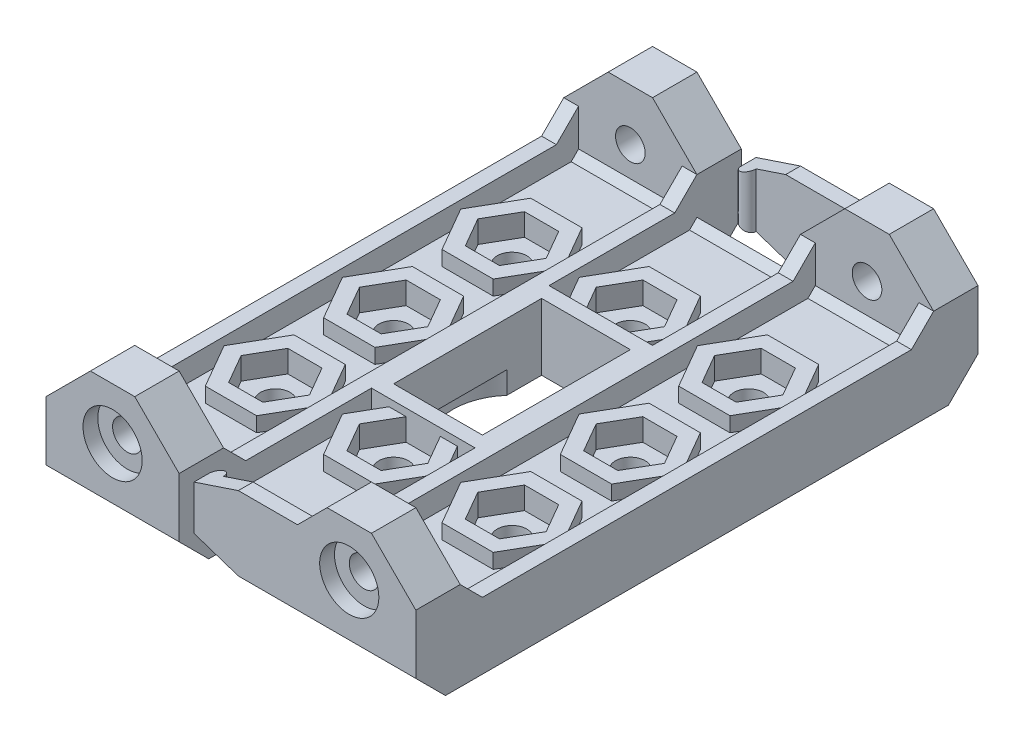
SolidWorks part; units mm, degrees
ref_plane "Front Plane" through (0, 0, 0) normal (0, 0, 1) x (1, 0, 0)
ref_plane "Top Plane" through (0, 0, 0) normal (0, 1, 0) x (1, 0, 0)
ref_plane "Right Plane" through (0, 0, 0) normal (1, 0, 0) x (0, 0, -1)
sketch "Sketch1" plane through (0, 0, 0) normal (0, 1, 0) x (1, 0, 0)
  line L0 (-12.5, -19) -> (-12.5, -12.75)
  line L1 (-12.5, 19) -> (12.5, 19)
  line L2 (-12.5, 19) -> (-12.5, 12.75)
  line L3 (-12.5, -19) -> (12.5, -19)
  line L4 (12.5, 19) -> (12.5, -19)
  line L5 (-14.5, 10.75) -> (-19, 10.75)
  line L7 (-14.5, -10.75) -> (-19, -10.75)
  line L8 (-24, 5.75) -> (-24, -5.75)
  line L9 (-22.342, 7.842) -> (-6.7508, -7.7492) construction
  line L10 (-3, 5) -> (3, 5)
  line L11 (-20.7704, -6.2704) -> (-8.3892, 6.1108) construction
  line L12 (-3, 5) -> (-3, -5)
  line L13 (-3, -5) -> (3, -5)
  line L14 (3, 5) -> (3, -5)
  arc A0 (-24, 5.75) -> (-19, 10.75) centre (-19, 5.75) cw
  arc A1 (-19, -10.75) -> (-24, -5.75) centre (-19, -5.75) cw
  arc A2 (-12.5, 12.75) -> (-14.5, 10.75) centre (-14.5, 12.75) cw
  arc A3 (-12.5, -12.75) -> (-14.5, -10.75) centre (-14.5, -12.75) ccw
  circle A4 centre (-14.5, 0) radius 1.5
  circle A5 centre (0, 8) radius 1
  circle A6 centre (8, 0) radius 1
  circle A7 centre (0, -8) radius 1
  circle A8 centre (-8, 0) radius 1
  circle A9 centre (-20.1569, 5.6569) radius 1
  circle A10 centre (-20.1569, -5.6569) radius 1
  circle A11 centre (-8.8431, -5.6569) radius 1
  circle A12 centre (-8.8431, 5.6569) radius 1
  circle A13 centre (8, 8) radius 1
  circle A14 centre (8, -8) radius 1
  dimension "D8" = 5
  dimension "D9" = 2
  dimension "D10" = 2
  dimension "D11" = 14.5
  dimension "D12" = 8
  dimension "D16" = 8
  dimension "D17" = 8
  dimension "D20" = 8
  dimension "D24" = 3
  dimension "D25" = 3
  dimension "D1" = 12.5
  dimension "D2" = 12.5
  dimension "D3" = 19
  dimension "D4" = 19
  dimension "D5" = 10.75
  dimension "D6" = 10.75
  dimension "D7" = 11.5
  dimension "D13" = 8
  dimension "D14" = 8
  dimension "D15" = 8
  dimension "D18" = 8
  dimension "D19" = 8
  dimension "D21" = 8
  dimension "D22" = 8
  dimension "D23" = 8
  dimension "D26" = 5
  dimension "D27" = 5
extrude "Extrude1" add sketch "Sketch1" along normal blind 3
sketch "Sketch2" plane through (0, 0, 0) normal (0, 1, 0) x (1, 0, 0)
  line L0 (-19.5597, -3.4261) -> (-17.9263, -5.0587)
  line L1 (-19.2603, -2.3108) -> (-16.8108, -4.7603)
  line L2 (-6.3937, 3.2074) -> (-9.7397, 2.3108)
  line L3 (-5.4971, 6.5534) -> (-6.3937, 3.2074)
  line L4 (-20.1569, 5.6569) -> (-8.8431, -5.6569) construction
  line L5 (-7.9466, 9.0029) -> (-5.4971, 6.5534)
  line L6 (-11.2926, 8.1063) -> (-7.9466, 9.0029)
  line L7 (-11.2926, 8.1063) -> (-12.1892, 4.7603)
  line L8 (-7.2104, 4.0234) -> (-9.4413, 3.4263)
  line L9 (-6.6122, 6.254) -> (-7.2104, 4.0234)
  line L10 (-8.2447, 7.8874) -> (-6.6122, 6.254)
  line L11 (-19.5597, -3.4261) -> (-21.7902, -4.0244)
  line L12 (-21.7902, -4.0244) -> (-22.3874, -6.2553)
  line L13 (-22.3874, -6.2553) -> (-20.754, -7.8878)
  line L14 (-20.754, -7.8878) -> (-18.5234, -7.2896)
  line L15 (-18.5234, -7.2896) -> (-17.9263, -5.0587)
  line L16 (-22.6063, -3.2074) -> (-19.2603, -2.3108)
  line L17 (-22.6063, -3.2074) -> (-23.5029, -6.5534)
  line L18 (-23.5029, -6.5534) -> (-21.0534, -9.0029)
  line L19 (-21.0534, -9.0029) -> (-17.7074, -8.1063)
  line L20 (-17.7074, -8.1063) -> (-16.8108, -4.7603)
  line L21 (-10.4756, 7.2902) -> (-8.2447, 7.8874)
  line L22 (-11.0739, 5.0597) -> (-10.4756, 7.2902)
  line L23 (-12.1892, 4.7603) -> (-9.7397, 2.3108)
  line L24 (-11.0739, 5.0597) -> (-9.4413, 3.4263)
  line L25 (-14.5, 13.9789) -> (-14.5, -13.8529) construction
  line L26 (-17.9261, 5.0597) -> (-19.5587, 3.4263)
  line L27 (-16.8108, 4.7603) -> (-19.2603, 2.3108)
  line L28 (-17.9261, 5.0597) -> (-18.5244, 7.2902)
  line L29 (-18.5244, 7.2902) -> (-20.7553, 7.8874)
  line L30 (-20.7553, 7.8874) -> (-22.3878, 6.254)
  line L31 (-22.3878, 6.254) -> (-21.7896, 4.0234)
  line L32 (-21.7896, 4.0234) -> (-19.5587, 3.4263)
  line L33 (-17.7074, 8.1063) -> (-16.8108, 4.7603)
  line L34 (-17.7074, 8.1063) -> (-21.0534, 9.0029)
  line L35 (-21.0534, 9.0029) -> (-23.5029, 6.5534)
  line L36 (-23.5029, 6.5534) -> (-22.6063, 3.2074)
  line L37 (-22.6063, 3.2074) -> (-19.2603, 2.3108)
  line L38 (-5.4971, 0) -> (-25.9289, 0) construction
  line L39 (-11.0739, -5.0597) -> (-9.4413, -3.4263)
  line L40 (-12.1892, -4.7603) -> (-9.7397, -2.3108)
  line L41 (-11.0739, -5.0597) -> (-10.4756, -7.2902)
  line L42 (-10.4756, -7.2902) -> (-8.2447, -7.8874)
  line L43 (-8.2447, -7.8874) -> (-6.6122, -6.254)
  line L44 (-6.6122, -6.254) -> (-7.2104, -4.0234)
  line L45 (-7.2104, -4.0234) -> (-9.4413, -3.4263)
  line L46 (-11.2926, -8.1063) -> (-12.1892, -4.7603)
  line L47 (-11.2926, -8.1063) -> (-7.9466, -9.0029)
  line L48 (-7.9466, -9.0029) -> (-5.4971, -6.5534)
  line L49 (-5.4971, -6.5534) -> (-6.3937, -3.2074)
  line L50 (-6.3937, -3.2074) -> (-9.7397, -2.3108)
  point P57 (-14.5, 0)
extrude "Extrude2" add sketch "Sketch2" along normal blind 4
sketch "Sketch5" plane through (0, 0, 0) normal (0, 1, 0) x (1, 0, 0)
  line L0 (-1.1547, 10) -> (1.1547, 10)
  line L1 (-8, 0) -> (8, 0) construction
  line L2 (4, 15.3149) -> (4, -11.4926) construction
  line L3 (-2.3094, -8) -> (-1.1547, -10)
  line L4 (-1.1547, -6) -> (-2.3094, -8)
  line L5 (1.1547, -6) -> (-1.1547, -6)
  line L6 (2.3094, -8) -> (1.1547, -6)
  line L7 (-3.4641, -8) -> (-1.7321, -11)
  line L8 (-1.7321, -5) -> (-3.4641, -8)
  line L9 (1.7321, -5) -> (-1.7321, -5)
  line L10 (3.4641, -8) -> (1.7321, -5)
  line L11 (-1.7321, 11) -> (1.7321, 11)
  line L12 (1.1547, 10) -> (2.3094, 8)
  line L13 (1.7321, -11) -> (3.4641, -8)
  line L14 (1.1547, -10) -> (2.3094, -8)
  line L15 (-1.7321, -11) -> (1.7321, -11)
  line L16 (1.7321, 11) -> (3.4641, 8)
  line L17 (3.4641, 8) -> (1.7321, 5)
  line L18 (1.7321, 5) -> (-1.7321, 5)
  line L19 (-1.7321, 5) -> (-3.4641, 8)
  line L20 (-3.4641, 8) -> (-1.7321, 11)
  line L21 (2.3094, 8) -> (1.1547, 6)
  line L22 (1.1547, 6) -> (-1.1547, 6)
  line L23 (-1.1547, 6) -> (-2.3094, 8)
  line L24 (-2.3094, 8) -> (-1.1547, 10)
  line L25 (-1.1547, -10) -> (1.1547, -10)
  line L26 (9.1547, -10) -> (6.8453, -10)
  line L27 (10.3094, 8) -> (9.1547, 10)
  line L28 (9.1547, 6) -> (10.3094, 8)
  line L29 (6.8453, 6) -> (9.1547, 6)
  line L30 (5.6906, 8) -> (6.8453, 6)
  line L31 (11.4641, 8) -> (9.7321, 11)
  line L32 (9.7321, 5) -> (11.4641, 8)
  line L33 (6.2679, 5) -> (9.7321, 5)
  line L34 (4.5359, 8) -> (6.2679, 5)
  line L35 (6.2679, 11) -> (4.5359, 8)
  line L36 (9.7321, -11) -> (6.2679, -11)
  line L37 (6.8453, -10) -> (5.6906, -8)
  line L38 (6.2679, -11) -> (4.5359, -8)
  line L39 (6.8453, 10) -> (5.6906, 8)
  line L40 (9.7321, 11) -> (6.2679, 11)
  line L41 (4.5359, -8) -> (6.2679, -5)
  line L42 (6.2679, -5) -> (9.7321, -5)
  line L43 (9.7321, -5) -> (11.4641, -8)
  line L44 (11.4641, -8) -> (9.7321, -11)
  line L45 (5.6906, -8) -> (6.8453, -6)
  line L46 (6.8453, -6) -> (9.1547, -6)
  line L47 (9.1547, -6) -> (10.3094, -8)
  line L48 (10.3094, -8) -> (9.1547, -10)
  line L49 (9.1547, 10) -> (6.8453, 10)
  line L50 (-4.9483, 4) -> (13.5301, 4) construction
  line L51 (9.1547, -2) -> (6.8453, -2)
  line L52 (9.7321, -3) -> (6.2679, -3)
  line L53 (6.8453, -2) -> (5.6906, 0)
  line L54 (6.2679, -3) -> (4.5359, 0)
  line L55 (4.5359, 0) -> (6.2679, 3)
  line L56 (6.2679, 3) -> (9.7321, 3)
  line L57 (9.7321, 3) -> (11.4641, 0)
  line L58 (11.4641, 0) -> (9.7321, -3)
  line L59 (5.6906, 0) -> (6.8453, 2)
  line L60 (6.8453, 2) -> (9.1547, 2)
  line L61 (9.1547, 2) -> (10.3094, 0)
  line L62 (10.3094, 0) -> (9.1547, -2)
  line L63 (0, 0) -> (-15.423, -15.423) construction
  line L64 (-10, -1.1547) -> (-10, 1.1547)
  line L65 (-11, -1.7321) -> (-11, 1.7321)
  line L66 (-10, 1.1547) -> (-8, 2.3094)
  line L67 (-11, 1.7321) -> (-8, 3.4641)
  line L68 (-8, 3.4641) -> (-5, 1.7321)
  line L69 (-5, 1.7321) -> (-5, -1.7321)
  line L70 (-5, -1.7321) -> (-8, -3.4641)
  line L71 (-8, -3.4641) -> (-11, -1.7321)
  line L72 (-8, 2.3094) -> (-6, 1.1547)
  line L73 (-6, 1.1547) -> (-6, -1.1547)
  line L74 (-6, -1.1547) -> (-8, -2.3094)
  line L75 (-8, -2.3094) -> (-10, -1.1547)
  circle A1 centre (0, 8) radius 1 construction
  dimension "D1" = 4
  dimension "D2" = 4
extrude "Extrude3" add sketch "Sketch5" along normal blind 4
sketch "Sketch7" plane through (0, 0, 0) normal (0, 1, 0) x (1, 0, 0)
  line L0 (-12.5, -19) -> (12.5, -19) construction
  line L1 (-12.5, 19) -> (-11.5, 19)
  line L2 (-12.5, 19) -> (-12.5, -19)
  line L3 (-12.5, -19) -> (-11.5, -19)
  line L4 (-11.5, 19) -> (-11.5, -19)
  line L5 (12.5, 19) -> (-12.5, 19) construction
  line L6 (-4.5, 19) -> (-3.5, 19)
  line L7 (-4.5, 19) -> (-4.5, -19)
  line L8 (-4.5, -19) -> (-3.5, -19)
  line L9 (-3.5, 19) -> (-3.5, 6)
  line L10 (3.5, -6) -> (3.5, -19)
  line L11 (3.5, 19) -> (4.5, 19)
  line L12 (3.5, 19) -> (3.5, 6)
  line L13 (3.5, -19) -> (4.5, -19)
  line L14 (4.5, 19) -> (4.5, -19)
  line L15 (12.5, 19) -> (11.5, 19)
  line L16 (12.5, 19) -> (12.5, -19)
  line L17 (12.5, -19) -> (11.5, -19)
  line L18 (11.5, 19) -> (11.5, -19)
  line L19 (3.5, 6) -> (-3.5, 6)
  line L20 (3.5, -6) -> (-3.5, -6)
  line L21 (-3, 5) -> (3, 5)
  line L22 (-3, 5) -> (-3, -5)
  line L23 (-3, -5) -> (3, -5)
  line L24 (3, 5) -> (3, -5)
  line L25 (-3.5, -6) -> (-3.5, -19)
  dimension "D1" = 7
  dimension "D2" = 1
  dimension "D3" = 7
  dimension "D4" = 1
  dimension "D5" = 7
extrude "Extrude4" add sketch "Sketch7" along normal blind 4.5
sketch "Sketch8" plane through (0, 0, 0) normal (0, 1, 0) x (1, 0, 0)
  line L0 (-11.5, 7.3324) -> (-11.5, 19) construction
  line L2 (-11.5, -19) -> (-11.5, -7.3324) construction
  line L3 (-11.5, -9.7489) -> (-11.5, -10.25)
  line L4 (-12, 9.2511) -> (-19, 9.2511)
  line L5 (-11.5, 9.7511) -> (-11.5, 10.2511)
  line L6 (-12, -9.2489) -> (-19, -9.2489)
  line L7 (-11.5, -19) -> (-11.5, 19) construction
  line L8 (-12, -10.75) -> (-19, -10.75)
  line L9 (-24, -5.75) -> (-24, 5.7511)
  line L10 (-19, 10.7511) -> (-12, 10.7511)
  line L12 (-22.5, 5.7511) -> (-22.5, -5.7489)
  arc A0 (-11.5, -9.7489) -> (-12, -9.2489) centre (-12, -9.7489) ccw
  arc A1 (-19, 9.2511) -> (-22.5, 5.7511) centre (-19, 5.7511) ccw
  arc A2 (-19, -9.2489) -> (-22.5, -5.7489) centre (-19, -5.7489) cw
  arc A3 (-24, 5.7511) -> (-19, 10.7511) centre (-19, 5.7511) cw
  arc A4 (-19, -10.75) -> (-24, -5.75) centre (-19, -5.75) cw
  arc A5 (-11.5, -10.25) -> (-12, -10.75) centre (-12, -10.25) cw
  arc A6 (-11.5, 9.7511) -> (-12, 9.2511) centre (-12, 9.7511) cw
  arc A7 (-11.5, 10.2511) -> (-12, 10.7511) centre (-12, 10.2511) ccw
  point P24 (-11.5, -9.2489)
  point P27 (-11.5, -10.75)
  point P30 (-11.5, 9.2511)
  point P33 (-11.5, 10.7511)
  dimension "D1" = 3.5
  dimension "D2" = 3.5
  dimension "D3" = 5
  dimension "D4" = 5
  dimension "D5" = 0.5
extrude "Extrude5" add sketch "Sketch8" along normal blind 6
sketch "Sketch9" plane through (0, 0, 0) normal (0, 1, 0) x (1, 0, 0)
  circle A0 centre (-14.5, 0) radius 5.5
  circle A1 centre (-14.5, 0) radius 1.5
extrude "Extrude10" add sketch "Sketch9" along normal blind 3.5
sketch "Sketch10" plane through (0, 0, 0) normal (0, 1, 0) x (1, 0, 0)
  line L0 (-16.2321, 3) -> (-12.7679, 3)
  line L2 (-16.9537, 4.25) -> (-12.0463, 4.25)
  line L14 (-12.0463, 4.25) -> (-9.5925, 0)
  line L15 (-12.7679, 3) -> (-11.0359, 0)
  line L16 (-11.0359, 0) -> (-12.7679, -3)
  line L17 (-12.7679, -3) -> (-16.2321, -3)
  line L18 (-16.2321, -3) -> (-17.9641, 0)
  line L19 (-17.9641, 0) -> (-16.2321, 3)
  line L20 (-9.5925, 0) -> (-12.0463, -4.25)
  line L21 (-12.0463, -4.25) -> (-16.9537, -4.25)
  line L22 (-16.9537, -4.25) -> (-19.4075, 0)
  line L23 (-19.4075, 0) -> (-16.9537, 4.25)
extrude "Extrude11" add sketch "Sketch10" along normal blind 6
sketch "Sketch12" plane through (0, 0, 0) normal (0, 1, 0) x (1, 0, 0)
  line L0 (-11.5, 4.6098) -> (-11.5, -4.6098)
  line L1 (-11.5, 7.3324) -> (-11.5, 4.0711) construction
  line L2 (-11.5, -4.0711) -> (-11.5, -7.3324) construction
  arc A0 (-11.5, -4.6098) -> (-11.5, 4.6098) centre (-14.5, 0) ccw
extrude "Extrude12" add sketch "Sketch12" along normal blind 4
sketch "Sketch13" plane through (0, 3.5, 0) normal (0, 1, 0) x (-1, 0, 0)
  line L0 (11.0359, 0) -> (12.7679, 3)
  line L1 (12.7679, 3) -> (16.2321, 3)
  line L2 (16.2321, 3) -> (17.9641, 0)
  line L3 (17.9641, 0) -> (16.2321, -3)
  line L4 (16.2321, -3) -> (12.7679, -3)
  line L5 (12.7679, -3) -> (11.0359, 0)
extrude "Cut-Extrude1" cut sketch "Sketch13" along normal blind 4
sketch "Sketch14" plane through (0, 3, 0) normal (0, 1, 0) x (-1, 0, 0)
  line L0 (8, -2.3094) -> (10, -1.1547)
  line L1 (10, -1.1547) -> (10, 1.1547)
  line L2 (10, 1.1547) -> (8, 2.3094)
  line L3 (8, 2.3094) -> (8, -2.3094)
extrude "Cut-Extrude2" cut sketch "Sketch14" along normal blind 4
sketch "Sketch16" plane through (0, 0, 19) normal (0, 0, 1) x (1, 0, 0)
  line L0 (-12.5, 4.5) -> (-12.5, 0) construction
  line L3 (12.5, 0) -> (12.5, 6)
  line L4 (12.5, 6) -> (9.5, 9)
  line L5 (-6.5, 9) -> (-3.5, 6)
  line L7 (-12.5, 0) -> (-12.5, 6)
  line L8 (-12.5, 6) -> (-9.5, 9)
  line L9 (9.5, 9) -> (6.5, 9)
  line L10 (6.5, 9) -> (4.5, 7)
  line L11 (-9.5, 9) -> (-6.5, 9)
  line L12 (-12.5, 0) -> (-3.5, 0)
  line L13 (3.5, 0) -> (12.5, 0)
  line L16 (4.5, 7) -> (0.5, 7)
  line L17 (-2.5, 6) -> (0.5, 7)
  line L18 (-2.5, 6) -> (-2.5, 3)
  line L19 (-2.5, 3) -> (0.5, 2)
  line L20 (0.5, 2) -> (3.5, 2)
  line L21 (3.5, 2) -> (3.5, 0)
  line L23 (-3.5, 0) -> (-3.5, 6)
  circle A0 centre (-8, 5.5) radius 1
  circle A1 centre (8, 5.5) radius 1
  point P0 (-12.5, 2.25)
  dimension "D2" = 16
  dimension "D1" = 4.5
extrude "Extrude13" add sketch "Sketch16" against normal blind 3
sketch "Sketch17" plane through (0, 0, 19) normal (0, 0, 1) x (1, 0, 0)
  line L0 (-2.5, 3) -> (0.5, 2)
  line L1 (0.5, 2) -> (4.5, 2)
  line L2 (4.5, 2) -> (4.5, 0)
  line L3 (-12.5, 0) -> (12.5, 0) construction
  line L4 (4.5, 0) -> (-3.5, 0)
  line L5 (-3.5, 3) -> (-2.5, 3)
  line L6 (-3.5, 3) -> (-3.5, 0)
  dimension "D1" = 2
extrude "Cut-Extrude4" cut sketch "Sketch17" against normal blind 3
sketch "Sketch18" plane through (0, 0, 0) normal (0, 1, 0) x (1, 0, 0)
  line L0 (-2.5, -16) -> (3.5, -16)
  line L1 (3.5, -16) -> (3.5, -18)
  line L2 (-2.5, -18) -> (-2.5, -16)
  line L3 (-2.5, -16) -> (-2.5, -19) construction
  line L4 (-1.5, -18) -> (3.5, -18)
  arc A0 (-1.5, -18) -> (-2.5, -18) centre (-2, -18) ccw
  dimension "D1" = 0.5
extrude "Cut-Extrude5" cut sketch "Sketch18" along normal through all
sketch "Sketch19" plane through (0, 0, 16) normal (0, 0, -1) x (-1, 0, 0)
  line L0 (-4.5, 7) -> (-3.5, 6)
  line L1 (-3.5, 7) -> (-3.5, 4.5) construction
  line L2 (-3.5, 6) -> (-3.5, 7)
  line L3 (-3.5, 7) -> (-4.5, 7)
extrude "Cut-Extrude6" cut sketch "Sketch19" against normal blind 2
sketch "Sketch20" plane through (12.5, 0, 0) normal (1, 0, 0) x (0, 0, -1)
  line L0 (-16, 3) -> (-15.5, 3)
  line L1 (-19, 0) -> (19, 0) construction
  line L2 (-16, 3) -> (-16, 3.5)
  line L3 (-16, 3.5) -> (-15.5, 3)
  dimension "D1" = 3
extrude "Extrude14" add sketch "Sketch20" against normal blind 25
sketch "Sketch21" plane through (12.5, 0, 0) normal (1, 0, 0) x (0, 0, -1)
  line L0 (-16, 6) -> (-14.5, 4.5)
  line L2 (-16, 4.5) -> (19, 4.5) construction
  line L3 (-14.5, 4.5) -> (-16, 4.5)
  line L4 (-16, 4.5) -> (-16, 6)
extrude "Extrude15" add sketch "Sketch21" against normal blind 1
sketch "Sketch22" plane through (4.5, 0, 0) normal (1, 0, 0) x (0, 0, -1)
  line L0 (-16, 6) -> (-14.5, 4.5)
  line L1 (-14.5, 4.5) -> (-16, 4.5)
  line L2 (-16, 4.5) -> (-16, 6)
extrude "Extrude17" add sketch "Sketch22" against normal blind 1
sketch "Sketch23" plane through (-3.5, 0, 0) normal (1, 0, 0) x (0, 0, -1)
  line L0 (-16, 6) -> (-14.5, 4.5)
  line L1 (-14.5, 4.5) -> (-16, 4.5)
  line L2 (-16, 4.5) -> (-10.25, 4.5) construction
  line L3 (-16, 4.5) -> (-6, 4.5) construction
  line L4 (-16, 4.5) -> (-16, 6)
extrude "Extrude18" add sketch "Sketch23" against normal blind 1
sketch "Sketch24" plane through (-11.5, 0, 0) normal (1, 0, 0) x (0, 0, -1)
  line L0 (-16, 6) -> (-14.5, 4.5)
  line L1 (-14.5, 4.5) -> (-16, 4.5)
  line L2 (-16, 4.5) -> (-16, 6)
extrude "Extrude19" add sketch "Sketch24" against normal blind 1
sketch "Sketch25" plane through (12.5, 0, 0) normal (1, 0, 0) x (0, 0, -1)
  line L0 (-19, 0) -> (-17, 0)
  line L1 (-19, 0) -> (19, 0) construction
  line L2 (-17, 0) -> (-19, 2)
  line L3 (-19, 2) -> (-19, 0)
extrude "Cut-Extrude7" cut sketch "Sketch25" against normal through all
sketch "Sketch26" plane through (0, 0, 19) normal (0, 0, 1) x (1, 0, 0)
  circle A0 centre (-8, 5.5) radius 2
  circle A1 centre (8, 5.5) radius 2
extrude "Cut-Extrude8" cut sketch "Sketch26" against normal blind 1
mirror "Mirror1" about plane through (0, 0, 0) normal (0, 0, 1) of "Cut-Extrude8", "Cut-Extrude7", "Extrude19", "Extrude18", "Extrude17", "Extrude15", "Extrude14", "Cut-Extrude6", "Cut-Extrude5", "Cut-Extrude4", "Extrude13"
sketch "Sketch27" plane through (0, 0, 0) normal (0, -1, 0) x (1, 0, 0)
  circle A0 centre (0, 0) radius 4
extrude "Cut-Extrude9" cut sketch "Sketch27" against normal blind 1.5
sketch "Sketch28" plane through (0, 0, 0) normal (0, -1, 0) x (1, 0, 0)
  circle A0 centre (-14.5, 0) radius 4
extrude "Cut-Extrude10" cut sketch "Sketch28" against normal blind 1
sketch "Sketch29" plane through (-24, 0, 0) normal (-1, 0, 0) x (0, 0, 1)
  line L0 (-2.5005, 6) -> (2.4995, 6)
  line L2 (-0.5005, 4) -> (0.4995, 4)
  arc A0 (-2.5005, 6) -> (-0.5005, 4) centre (-0.5005, 6) ccw
  arc A2 (0.4995, 4) -> (2.4995, 6) centre (0.4995, 6) ccw
  dimension "D2" = 2
extrude "Cut-Extrude11" cut sketch "Sketch29" against normal blind 1.5
fillet "Fillet4" radius 0.25 13 edges at (-11.0231, 6, 2.4779) (-14.5, 6, 4.25) (-18.1806, 6, 2.125) (-18.1806, 6, -2.125) (-14.5, 6, -4.25) (-11.0231, 6, -2.4779) (-10, 6, 0) (-17.0981, 6, 1.5) (-14.5, 6, 3) (-11.9019, 6, 1.5) (-11.9019, 6, -1.5) (-14.5, 6, -3) (-17.0981, 6, -1.5)
sketch "Sketch30" plane through (0, 3.5, 0) normal (0, 1, 0) x (-1, 0, 0)
  line L0 (16.2321, -3) -> (12.7679, -3)
  line L1 (12.7679, -3) -> (11.0359, 0)
  line L2 (4.95, 0) -> (-4.95, 0) construction
  line L3 (11.0359, 0) -> (12.7679, 3) construction
  line L4 (11.0359, 0) -> (12.7679, 3)
  line L5 (16.2321, 3) -> (17.9641, 0)
  line L6 (17.9641, 0) -> (16.2321, 3) construction
  line L7 (17.9641, 0) -> (16.2321, -3)
  line L8 (12.7679, 3) -> (11.0359, 0) construction
  line L9 (12.7679, 3) -> (16.2321, 3)
extrude "Cut-Extrude12" cut sketch "Sketch30" against normal blind 1.5
sketch "Sketch31" plane through (0, 0, 0) normal (0, -1, 0) x (1, 0, 0)
  line L0 (-12.5, -19) -> (-12.5, 19)
  line L1 (-12.5, 19) -> (-28.5028, 19)
  line L2 (-28.5028, 19) -> (-28.5028, -19)
  line L3 (-28.5028, -19) -> (-12.5, -19)
extrude "Cut-Extrude13" cut sketch "Sketch31" against normal through all
sketch "Sketch32" plane through (0, 0, 0) normal (0, 0, -1) x (-1, 0, 0)
  line L12 (0, 12.6124) -> (0, -2.6165) construction
  line L13 (12.8379, 9.6424) -> (4.5, 4.5)
  line L14 (12.8379, 4.5) -> (12.8379, 9.6424)
  line L15 (11.5, 4.5) -> (12.8379, 4.5)
  line L16 (11.5, 3) -> (11.5, 4.5)
  line L17 (4.5, 3) -> (11.5, 3)
  line L18 (4.5, 4.5) -> (4.5, 3)
extrude "Cut-Extrude14" cut sketch "Sketch32" along normal blind 14.5 and the other way blind 14.5
sketch "Sketch33" plane through (0, 0, 0) normal (0, 0, 1) x (1, 0, 0)
  line L1 (-12.5, 0) -> (-3.5, 0) construction
  line L2 (-4.5, 0) -> (-12.5, 0)
  line L3 (-12.5, 0) -> (-12.5, 4.5)
  line L4 (-12.5, 4.5) -> (-11.5, 4.5)
  line L5 (-12.5, 4.5) -> (-11.5, 4.5) construction
  line L6 (-11.5, 6) -> (-11.5, 3.5) construction
  line L7 (-11.5, 4.5) -> (-11.5, 3)
  line L8 (-11.5, 3) -> (-4.5, 3) construction
  line L9 (-11.0359, 3) -> (-11.5, 3) construction
  line L10 (-11.5, 3) -> (-4.5, 3)
  line L11 (-4.5, 3) -> (-4.5, 3.5) construction
  line L12 (-4.5, 3) -> (-4.5, 0)
extrude "Extrude20" add sketch "Sketch33" along normal blind 15 and the other way blind 15
sketch "Sketch34" plane through (0, 3, 0) normal (0, 1, 0) x (-1, 0, 0)
  line L40 (0, -20.1599) -> (0, 21.0169) construction
  line L41 (6.8453, 6) -> (5.6906, 8)
  line L42 (9.1547, 6) -> (6.8453, 6)
  line L43 (10.3094, 8) -> (9.1547, 6)
  line L44 (9.1547, 10) -> (10.3094, 8)
  line L45 (6.8453, 10) -> (9.1547, 10)
  line L46 (5.6906, 8) -> (6.8453, 10)
  line L47 (6.2679, 5) -> (4.5359, 8)
  line L48 (9.7321, 5) -> (6.2679, 5)
  line L49 (11.4641, 8) -> (9.7321, 5)
  line L50 (9.7321, 11) -> (11.4641, 8)
  line L51 (6.2679, 11) -> (9.7321, 11)
  line L52 (4.5359, 8) -> (6.2679, 11)
  line L53 (6.8453, -2) -> (5.6906, 0)
  line L54 (9.1547, -2) -> (6.8453, -2)
  line L55 (10.3094, 0) -> (9.1547, -2)
  line L56 (9.1547, 2) -> (10.3094, 0)
  line L57 (6.8453, 2) -> (9.1547, 2)
  line L58 (5.6906, 0) -> (6.8453, 2)
  line L59 (6.2679, -3) -> (4.5359, 0)
  line L60 (9.7321, -3) -> (6.2679, -3)
  line L61 (11.4641, 0) -> (9.7321, -3)
  line L62 (9.7321, 3) -> (11.4641, 0)
  line L63 (6.2679, 3) -> (9.7321, 3)
  line L64 (4.5359, 0) -> (6.2679, 3)
  line L65 (6.2679, -11) -> (4.5359, -8)
  line L66 (9.7321, -11) -> (6.2679, -11)
  line L67 (11.4641, -8) -> (9.7321, -11)
  line L68 (9.7321, -5) -> (11.4641, -8)
  line L69 (6.2679, -5) -> (9.7321, -5)
  line L70 (4.5359, -8) -> (6.2679, -5)
  line L71 (6.8453, -10) -> (5.6906, -8)
  line L72 (9.1547, -10) -> (6.8453, -10)
  line L73 (10.3094, -8) -> (9.1547, -10)
  line L74 (9.1547, -6) -> (10.3094, -8)
  line L75 (6.8453, -6) -> (9.1547, -6)
  line L76 (5.6906, -8) -> (6.8453, -6)
extrude "Extrude21" add sketch "Sketch34" along normal blind 1
sketch "Sketch35" plane through (0, 3, 0) normal (0, 1, 0) x (-1, 0, 0)
  line L0 (10.3094, -8) -> (9.1547, -6)
  line L1 (9.1547, -6) -> (6.8453, -6)
  line L2 (5.6906, -8) -> (6.8453, -6)
  line L3 (5.6906, -8) -> (6.8453, -10)
  line L4 (6.8453, -10) -> (9.1547, -10)
  line L5 (9.1547, -10) -> (10.3094, -8)
  line L6 (10.3094, 0) -> (9.1547, 2)
  line L7 (4.95, 0) -> (-4.95, 0) construction
  line L8 (9.1547, 2) -> (6.8453, 2)
  line L9 (6.8453, 2) -> (5.6906, 0)
  line L10 (-2.3094, -8) -> (-1.1547, -6)
  line L11 (5.6906, 0) -> (6.8453, -2) construction
  line L12 (6.8453, -2) -> (9.1547, -2)
  line L13 (9.1547, -2) -> (10.3094, 0)
  line L14 (10.3094, 8) -> (9.1547, 10)
  line L15 (9.1547, 10) -> (6.8453, 10)
  line L16 (6.8453, 10) -> (5.6906, 8)
  line L17 (5.6906, 8) -> (6.8453, 6)
  line L18 (6.8453, 6) -> (9.1547, 6)
  line L19 (9.1547, 6) -> (10.3094, 8)
  line L20 (5.6906, 0) -> (6.8453, -2)
  line L21 (-1.1547, 6) -> (1.1547, 6)
  line L22 (1.1547, 6) -> (2.3094, 8)
  line L23 (2.3094, 8) -> (1.1547, 10)
  line L24 (1.1547, 10) -> (-1.1547, 10)
  line L25 (-1.1547, 10) -> (-2.3094, 8)
  line L26 (-2.3094, 8) -> (-1.1547, 6)
  line L27 (-14.7215, 0) -> (17.2529, 0) construction
  line L28 (-1.1547, -10) -> (-2.3094, -8)
  line L29 (1.1547, -10) -> (-1.1547, -10)
  line L30 (2.3094, -8) -> (1.1547, -10)
  line L31 (1.1547, -6) -> (2.3094, -8)
  line L32 (-1.1547, -6) -> (1.1547, -6)
  line L33 (0, 14.0685) -> (0, -14.4118) construction
  line L34 (-5.6906, 0) -> (-6.8453, -2)
  line L35 (-9.1547, 6) -> (-10.3094, 8)
  line L36 (-6.8453, 6) -> (-9.1547, 6)
  line L37 (-5.6906, 8) -> (-6.8453, 6)
  line L38 (-6.8453, 10) -> (-5.6906, 8)
  line L39 (-9.1547, 10) -> (-6.8453, 10)
  line L40 (-10.3094, 8) -> (-9.1547, 10)
  line L41 (-9.1547, -2) -> (-10.3094, 0)
  line L42 (-6.8453, -2) -> (-9.1547, -2)
  line L43 (-6.8453, 2) -> (-5.6906, 0)
  line L44 (-9.1547, 2) -> (-6.8453, 2)
  line L45 (-10.3094, 0) -> (-9.1547, 2)
  line L46 (-9.1547, -10) -> (-10.3094, -8)
  line L47 (-6.8453, -10) -> (-9.1547, -10)
  line L48 (-5.6906, -8) -> (-6.8453, -10)
  line L49 (-5.6906, -8) -> (-6.8453, -6)
  line L50 (-9.1547, -6) -> (-6.8453, -6)
  line L51 (-10.3094, -8) -> (-9.1547, -6)
extrude "Cut-Extrude15" cut sketch "Sketch35" against normal blind 0.5
sketch "Sketch36" plane through (0, 0, 0) normal (0, -1, 0) x (1, 0, 0)
  line L0 (4.95, 0) -> (-4.95, 0) construction
  circle A0 centre (-8, 8) radius 1
  circle A1 centre (-8, 0) radius 1
  circle A2 centre (-8, -8) radius 1
  circle A3 centre (0, 8) radius 1 construction
  circle A4 centre (0, -8) radius 1 construction
  dimension "D1" = 8
  dimension "D2" = 8
  dimension "D3" = 8
  dimension "D5" = 8
  dimension "D4" = 8
extrude "Cut-Extrude16" cut sketch "Sketch36" against normal blind 10.5
